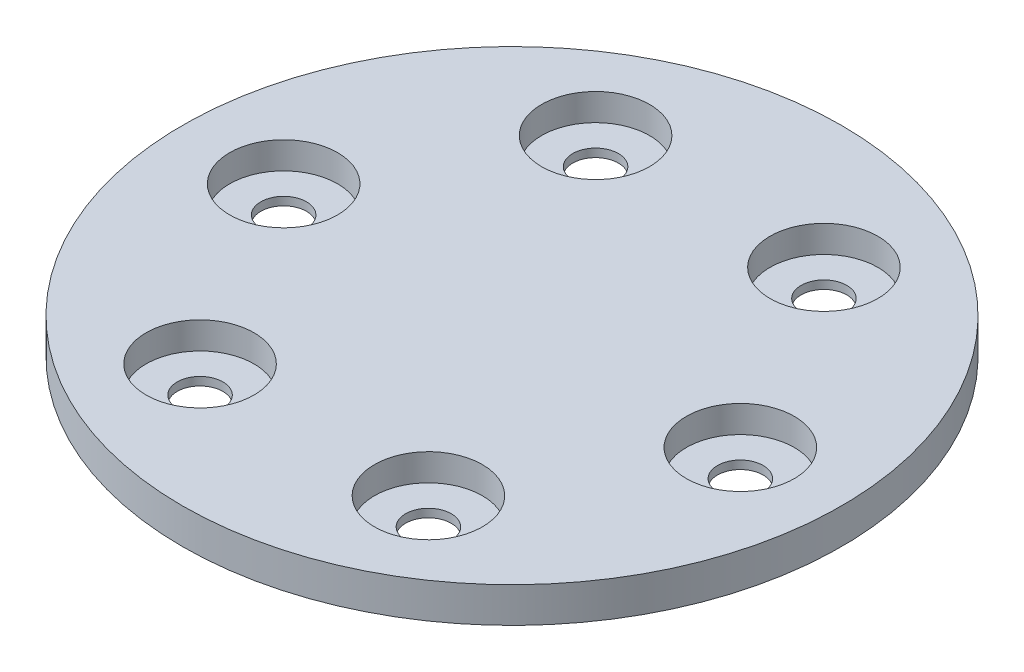
SolidWorks part; units mm, degrees
material "1060 Alloy"
ref_plane "Front Plane" through (0, 0, 0) normal (0, 0, 1) x (1, 0, 0)
ref_plane "Top Plane" through (0, 0, 0) normal (0, 1, 0) x (1, 0, 0)
ref_plane "Right Plane" through (0, 0, 0) normal (1, 0, 0) x (0, 0, -1)
sketch "Sketch1" plane through (0, 0, 0) normal (0, 1, 0) x (1, 0, 0)
  circle A0 centre (0, 0) radius 15.875
  dimension "D1" = 31.75
extrude "Boss-Extrude1" add sketch "Sketch1" along normal blind 1.7
sketch "Sketch3" plane through (0, 1.7, 0) normal (0, 1, 0) x (1, 0, 0)
  circle A0 centre (0, -10.25) radius 0.25
  circle A1 centre (0, 0) radius 9.8
  dimension "D1" = 0.5
  dimension "D2" = 10.25
  dimension "D3" = 19.6
sketch "Sketch4" plane through (0, 1.7, 0) normal (0, -1, 0) x (1, 0, 0)
  line L0 (0, 0) -> (13.2597, 13.2597) construction
  circle A0 centre (7.7782, 7.7782) radius 1
  dimension "D2" = 2
  dimension "D1" = 11
sketch "Sketch5" plane through (0, 1.7, 0) normal (0, 1, 0) x (1, 0, 0)
  circle A0 centre (0, 0) radius 11
  dimension "D1" = 22
hole_wizard "CBORE for M5 Hex Head Bolt1" positions "Sketch6" profile "Sketch7" counterbore size "M5" standard "ISO"
sketch "Sketch6" plane through (0, 1.7, 0) normal (0, 1, 0) x (1, 0, 0)
  point P0 (11, 0)
  dimension "D1" = 11
sketch "Sketch7" plane through (11, 1.7, 0) normal (1, 0, 0) x (0, 0, 1)
  line L0 (0, 0) -> (0, 5.6609)
  line L1 (0, 5.6609) -> (1.1, 5)
  line L2 (1.1, 5) -> (1.1, 1.3)
  line L3 (1.1, 1.3) -> (2.6, 1.3)
  line L4 (2.6, 1.3) -> (2.6, 0)
  line L5 (2.6, 0) -> (0, 0)
  line L10 (0, 5.6609) -> (-1.1, 5) construction
  line L11 (0, -6.35) -> (0, 107.95) construction
  dimension "Hole Dia." = 2.2
  dimension "Hole Depth" = 5
  dimension "C'Bore Dia." = 5.2
  dimension "C'Bore Depth" = 1.3
  dimension "Drill Angle" = 118
pattern_circular "CirPattern1" count 6 over 360 about axis through (0, 1.7, 0) along (0, 1, 0) of "CBORE for M5 Hex Head Bolt1"
